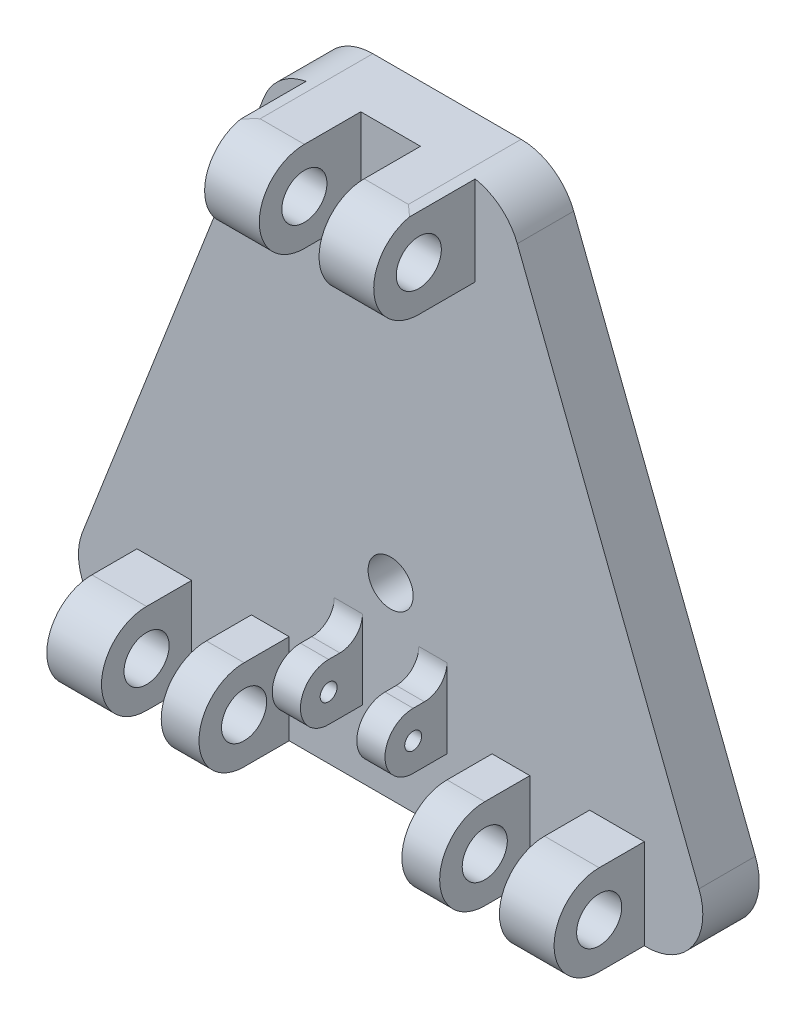
SolidWorks part; units mm, degrees
ref_plane "Front Plane" through (0, 0, 0) normal (0, 0, 1) x (1, 0, 0)
ref_plane "Top Plane" through (0, 0, 0) normal (0, 1, 0) x (1, 0, 0)
ref_plane "Right Plane" through (0, 0, 0) normal (1, 0, 0) x (0, 0, -1)
sketch "Sketch1" plane through (0, 0, 0) normal (0, 0, 1) x (1, 0, 0)
  line L1 (-30, -28.625) -> (30, -28.625)
  line L2 (-30, -28.625) -> (-10, 22.875)
  line L3 (-10, 22.875) -> (10, 22.875)
  line L4 (30, -28.625) -> (10, 22.875)
  line L5 (-30, -28.625) -> (10, 22.875) construction
  line L6 (-10, 22.875) -> (30, -28.625) construction
  point P0 (0, 10)
  point P6 (-10.0357, -30.3959)
  point P7 (-10.5366, -30.8925)
  point P8 (0, 0)
  point P9 (0, 10.5137)
  point P11 (0, 0)
  dimension "D1" = 51.5
  dimension "D2" = 60
  dimension "D3" = 20
  dimension "D4" = 10
extrude "Boss-Extrude1" add sketch "Sketch1" along normal mid plane 5
sketch "Sketch2" plane through (0, 0, 0) normal (1, 0, 0) x (0, 0, -1)
  line L0 (-2.5, -28.625) -> (-6.5, -28.625)
  line L1 (-2.5, -28.625) -> (-2.5, 22.875) construction
  line L2 (-6.5, -20.625) -> (-2.5, -20.625)
  line L3 (-2.5, -20.625) -> (-2.5, -28.625)
  line L4 (-2.5, -28.625) -> (2.5, -28.625) construction
  arc A0 (-6.5, -28.625) -> (-6.5, -20.625) centre (-6.5, -24.625) cw
  circle A1 centre (-6.5, -24.625) radius 2
  dimension "D1" = 4
  dimension "D2" = 4
  dimension "D3" = 4
extrude "Boss-Extrude2" add sketch "Sketch2" along normal mid plane 45
sketch "Sketch3" plane through (0, -28.625, 0) normal (0, -1, 0) x (1, 0, 0)
  line L0 (22.5, 10.5) -> (-22.5, 10.5) construction
  line L1 (-9, 18.5) -> (9, 18.5)
  line L2 (-9, 18.5) -> (-9, 2.5)
  line L3 (-9, 2.5) -> (9, 2.5)
  line L4 (9, 18.5) -> (9, 2.5)
  line L5 (-9, 18.5) -> (9, 2.5) construction
  line L6 (-9, 2.5) -> (9, 18.5) construction
  line L7 (22.5, 2.5) -> (30, 2.5) construction
  line L8 (22.5, 10.5) -> (-22.5, 10.5) construction
  line L9 (-17.65, 18.5) -> (-12.35, 18.5)
  line L10 (-17.65, 18.5) -> (-17.65, 2.5)
  line L11 (-17.65, 2.5) -> (-12.35, 2.5)
  line L12 (-12.35, 18.5) -> (-12.35, 2.5)
  line L13 (-17.65, 18.5) -> (-12.35, 2.5) construction
  line L14 (-17.65, 2.5) -> (-12.35, 18.5) construction
  point P0 (0, 10.5)
  point P9 (-15, 10.5)
  dimension "D1" = 18
  dimension "D2" = 5.3
  dimension "D3" = 15
extrude "Cut-Extrude1" cut sketch "Sketch3" against normal up to surface (28.625 mm away) up to plane "Top Plane"
mirror "Mirror2" about plane through (0, 0, 0) normal (1, 0, 0) of "Cut-Extrude1"
mirror "Mirror1" [suppressed] about plane through (0, 0, 0) normal (0, 1, 0)
sketch "Sketch7" plane through (0, 0, 0) normal (1, 0, 0) x (0, 0, -1)
  line L0 (-2.5, 14.875) -> (-7.5, 14.875)
  line L1 (-2.5, -28.625) -> (-2.5, 22.875) construction
  line L2 (-7.5, 22.875) -> (-2.5, 22.875)
  line L3 (-2.5, 22.875) -> (-2.5, 14.875)
  line L4 (-2.5, 22.875) -> (2.5, 22.875) construction
  arc A0 (-7.5, 14.875) -> (-7.5, 22.875) centre (-7.5, 18.875) cw
  circle A1 centre (-7.5, 18.875) radius 2
  dimension "D1" = 4
  dimension "D2" = 4
  dimension "D3" = 5
extrude "Boss-Extrude4" add sketch "Sketch7" along normal mid plane 15
sketch "Sketch8" plane through (0, 22.875, 0) normal (0, 1, 0) x (1, 0, 0)
  line L0 (-7.5, -11.5) -> (7.5, -11.5) construction
  line L1 (-2.65, -20.5) -> (2.65, -20.5)
  line L2 (-2.65, -20.5) -> (-2.65, -2.5)
  line L3 (-2.65, -2.5) -> (2.65, -2.5)
  line L4 (2.65, -20.5) -> (2.65, -2.5)
  line L5 (-2.65, -20.5) -> (2.65, -2.5) construction
  line L6 (-2.65, -2.5) -> (2.65, -20.5) construction
  line L7 (10, -2.5) -> (7.5, -2.5) construction
  point P0 (0, -11.5)
  dimension "D1" = 5.3
extrude "Cut-Extrude4" cut sketch "Sketch8" against normal up to surface (8 mm away) up to face at (0, 14.875, 5)
sketch "Sketch4" plane through (0, 0, 0) normal (1, 0, 0) x (0, 0, -1)
  line L0 (-2.5, -22.625) -> (-5.5, -22.625)
  line L1 (-2.5, -28.625) -> (-2.5, 22.875) construction
  line L2 (-5.5, -17.625) -> (-2.5, -17.625)
  line L3 (-2.5, -17.625) -> (-2.5, -22.625)
  line L5 (-2.5, -28.625) -> (2.5, -28.625) construction
  arc A0 (-5.5, -22.625) -> (-5.5, -17.625) centre (-5.5, -20.125) cw
  circle A1 centre (-5.5, -20.125) radius 0.75
  dimension "D1" = 1.5
  dimension "D2" = 2.5
  dimension "D3" = 3
  dimension "D4" = 6
extrude "Boss-Extrude3" add sketch "Sketch4" along normal mid plane 10
sketch "Sketch5" plane through (0, -17.625, 0) normal (0, 1, 0) x (1, 0, 0)
  line L0 (-5, -8) -> (5, -8) construction
  line L1 (-2.5, -13.5) -> (2.5, -13.5)
  line L2 (-2.5, -13.5) -> (-2.5, -2.5)
  line L3 (-2.5, -2.5) -> (2.5, -2.5)
  line L4 (2.5, -13.5) -> (2.5, -2.5)
  line L5 (-2.5, -13.5) -> (2.5, -2.5) construction
  line L6 (-2.5, -2.5) -> (2.5, -13.5) construction
  line L8 (10, -2.5) -> (7.5, -2.5) construction
  point P0 (0, -8)
  point P9 (0, 0)
  dimension "D1" = 5
extrude "Cut-Extrude2" cut sketch "Sketch5" against normal through all
fillet "Fillet1" [suppressed] radius 3
fillet "Fillet2" radius 2 2 edges at (3.75, -17.625, 2.5) (-3.75, -17.625, 2.5)
sketch "Sketch6" plane through (0, 0, 2.5) normal (0, 0, 1) x (1, 0, 0)
  circle A0 centre (0, -12) radius 2
  point P3 (0, 0)
  point P4 (0, -7.6297)
  dimension "D1" = 4
  dimension "D2" = 12
extrude "Cut-Extrude3" cut sketch "Sketch6" against normal through all
fillet "Fillet4" radius 5 4 edges at (30, -28.625, 0) (-30, -28.625, 0) (10, 22.875, 0) (-10, 22.875, 0)
